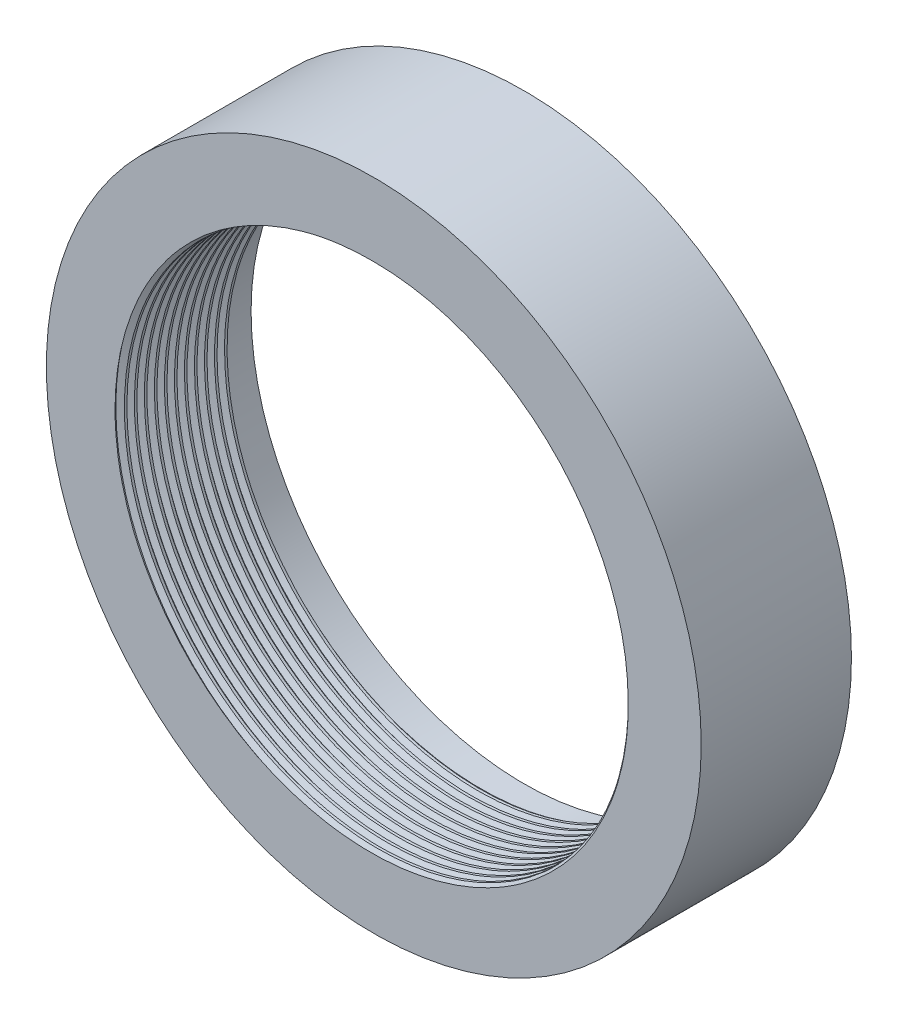
SolidWorks part; units mm, degrees
ref_plane "前视基准面" through (0, 0, 0) normal (0, 0, 1) x (1, 0, 0)
ref_plane "上视基准面" through (0, 0, 0) normal (0, 1, 0) x (1, 0, 0)
ref_plane "右视基准面" through (0, 0, 0) normal (1, 0, 0) x (0, 0, -1)
sketch "草图1" plane through (0, 0, 0) normal (0, 0, 1) x (1, 0, 0)
  circle A0 centre (0, 0) radius 25.4
  circle A1 centre (0, 0) radius 32.69
  dimension "D1" = 50.8
  dimension "D2" = 65.38
extrude "凸台-拉伸1" add sketch "草图1" along normal blind 15 contours A1
sketch "草图2" plane through (0, 0, 0) normal (0, 0, -1) x (-1, 0, 0)
  circle A0 centre (0, 0) radius 25.4
extrude "切除-拉伸1" cut sketch "草图2" against normal up to next
thread "螺纹线1" pitch 1 method cut profile "螺纹线轮廓1" start angle 0, offset 0, length 0, pitch 1, diameter 50.8
ref_plane "基准面4" through (25.4, 0, 0) normal (0, -1, 0) x (1, 0, 0)
sketch "螺纹线轮廓1" plane through (25.4, 0, 0) normal (0, -1, 0) x (1, 0, 0)
  line L0 (0, 0) -> (0, 1) construction
  line L1 (0, 0) -> (0.5413, 0.3125)
  line L2 (0.5413, 0.3125) -> (0.5413, 0.4375)
  line L3 (0.5413, 0.4375) -> (0, 0.75)
  line L4 (0.5413, 0.375) -> (0, 0.375) construction
  line L11 (0, 0) -> (0, 0.75)
  point P2 (0, 0)
  dimension "Pitch" = 1
  dimension "Profile_Angle" = 60
  dimension "Profile_Land" = 0.125
  dimension "Profile_Height" = 0.5413
sketch "草图3" plane through (0, 0, 0) normal (0, 0, -1) x (-1, 0, 0)
  circle A0 centre (0, 0) radius 27.25
  dimension "D1" = 54.5
extrude "切除-拉伸2" cut sketch "草图3" against normal blind 4
sketch "草图4" plane through (0, 0, 0) normal (0, 0, -1) x (-1, 0, 0)
  line L0 (0, 0) -> (-21.7174, 16.4595) construction
  line L1 (-23.8852, 18.1025) -> (23.6148, 18.1025)
  line L2 (-23.8852, 18.1025) -> (-23.8852, -17.8975)
  line L3 (-23.8852, -17.8975) -> (23.6148, -17.8975)
  line L4 (23.6148, 18.1025) -> (23.6148, -17.8975)
  line L5 (-21.7174, 16.4595) -> (-26.0529, 19.7454) construction
  line L6 (0, 0) -> (23.6148, -17.8975) construction
  circle A0 centre (0, 0) radius 27.25 construction
  circle A1 centre (0, 0) radius 32.69 construction
  point P12 (-23.8852, 18.1025)
  dimension "D1" = 36
  dimension "D2" = 47.5
